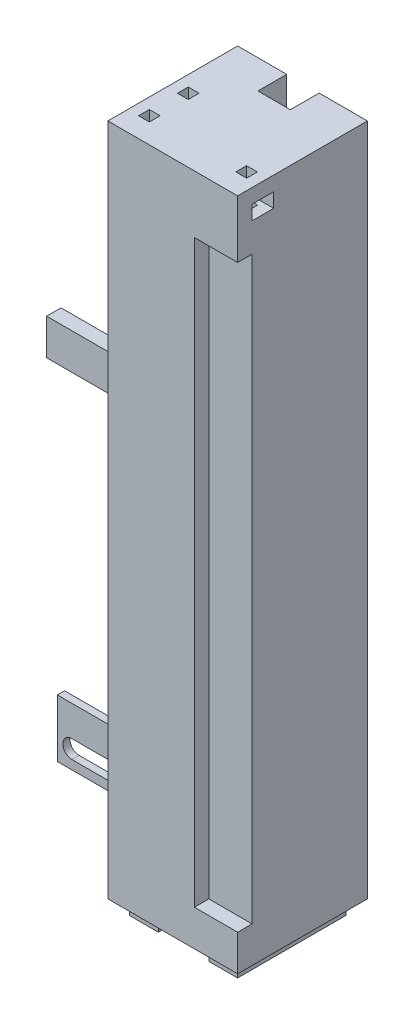
SolidWorks part; units mm, degrees
ref_plane "Front Plane" through (0, 0, 0) normal (0, 0, 1) x (1, 0, 0)
ref_plane "Top Plane" through (0, 0, 0) normal (0, 1, 0) x (1, 0, 0)
ref_plane "Right Plane" through (0, 0, 0) normal (1, 0, 0) x (0, 0, -1)
sketch "Sketch1" plane through (0, 0, 0) normal (0, 1, 0) x (1, 0, 0)
  line L1 (0, 0) -> (36, 0)
  line L2 (0, 0) -> (0, 36)
  line L3 (0, 36) -> (36, 36)
  line L4 (36, 0) -> (36, 36)
  dimension "D1" = 36
  dimension "D2" = 36
extrude "Boss-Extrude1" add sketch "Sketch1" along normal blind 186.9
sketch "Sketch2" plane through (0, 0, 0) normal (0, -1, 0) x (1, 0, 0)
  line L0 (0, 0) -> (36, 0) construction
  line L1 (3, -3) -> (7, -3)
  line L2 (3, -3) -> (3, -33)
  line L3 (3, -33) -> (7, -33)
  line L4 (7, -11) -> (7, -25)
  line L5 (36, -36) -> (0, -36) construction
  line L6 (0, -36) -> (0, 0) construction
  line L20 (36, 0) -> (36, -36) construction
  line L29 (7, -3) -> (11, -3)
  line L31 (7, -11) -> (11, -11)
  line L32 (11, -3) -> (11, -11)
  line L33 (7, -25) -> (11, -25)
  line L35 (7, -33) -> (11, -33)
  line L36 (11, -25) -> (11, -33)
  line L45 (29, -3) -> (33, -3)
  line L46 (29, -11) -> (29, -25)
  line L47 (29, -33) -> (33, -33)
  line L48 (33, -3) -> (33, -33)
  line L50 (29, -3) -> (25, -3)
  line L52 (29, -11) -> (25, -11)
  line L53 (25, -3) -> (25, -11)
  line L54 (29, -33) -> (25, -33)
  line L56 (29, -25) -> (25, -25)
  line L57 (25, -33) -> (25, -25)
  dimension "D1" = 3
  dimension "D2" = 3
  dimension "D3" = 3
  dimension "D4" = 4
  dimension "D5" = 4
  dimension "D6" = 8
  dimension "D7" = 8
  dimension "D8" = 4
  dimension "D9" = 3
  dimension "D10" = 3
  dimension "D11" = 3
  dimension "D12" = 4
  dimension "D13" = 4
  dimension "D14" = 4
extrude "Boss-Extrude2" add sketch "Sketch2" along normal blind 4
sketch "Sketch3" plane through (0, 0, 0) normal (0, -1, 0) x (1, 0, 0)
  line L0 (36, -36) -> (0, -36) construction
  line L2 (0, -36) -> (0, 0) construction
  circle A0 centre (18, -18) radius 2
  dimension "D1" = 4
  dimension "D2" = 18
  dimension "D3" = 18
extrude "Cut-Extrude1" cut sketch "Sketch3" against normal blind 5
sketch "Sketch4" plane through (0, 0, -36) normal (0, 0, 1) x (1, 0, 0)
  line L0 (0, 186.9) -> (36, 186.9) construction
  line L1 (13.62, 186.9) -> (22.62, 186.9)
  line L2 (13.62, 186.9) -> (13.62, 0)
  line L3 (13.62, 0) -> (22.62, 0)
  line L4 (22.62, 186.9) -> (22.62, 0)
  line L5 (0, 0) -> (36, 0) construction
  line L7 (36, 186.9) -> (36, 0) construction
  dimension "D1" = 13.38
  dimension "D2" = 9
extrude "Cut-Extrude2" cut sketch "Sketch4" along normal blind 8
sketch "Sketch5" plane through (36, 0, 0) normal (1, 0, 0) x (0, 0, -1)
  line L0 (0, 186.9) -> (36, 186.9) construction
  line L1 (4, 182.9) -> (10, 182.9)
  line L2 (4, 182.9) -> (4, 178.9)
  line L3 (4, 178.9) -> (10, 178.9)
  line L4 (10, 182.9) -> (10, 178.9)
  line L5 (0, 186.9) -> (0, 0) construction
  dimension "D1" = 6
  dimension "D2" = 4
  dimension "D3" = 4
  dimension "D4" = 4
extrude "Cut-Extrude3" cut sketch "Sketch5" against normal blind 9
sketch "Sketch6" plane through (0, 186.9, 0) normal (0, 1, 0) x (1, 0, 0)
  line L0 (36, 0) -> (36, 36) construction
  line L1 (30, 8.5) -> (33, 8.5)
  line L2 (30, 8.5) -> (30, 5.5)
  line L3 (30, 5.5) -> (33, 5.5)
  line L4 (33, 8.5) -> (33, 5.5)
  line L5 (0, 0) -> (36, 0) construction
  dimension "D1" = 3
  dimension "D2" = 3
  dimension "D3" = 3
  dimension "D4" = 5.5
extrude "Cut-Extrude4" cut sketch "Sketch6" against normal blind 10
sketch "Sketch7" plane through (0, 0, 0) normal (-1, 0, 0) x (0, 0, 1)
  line L0 (-36, 186.9) -> (-36, 0) construction
  line L1 (-28, 0) -> (-26, 0)
  line L2 (-28, 0) -> (-28, 16)
  line L3 (-28, 16) -> (-26, 16)
  line L4 (-26, 0) -> (-26, 16)
  dimension "D1" = 2
  dimension "D2" = 16
  dimension "D3" = 8
extrude "Boss-Extrude3" add sketch "Sketch7" along normal blind 40
sketch "Sketch8" plane through (0, 0, -26) normal (0, 0, 1) x (1, 0, 0)
  line L0 (-40, 0) -> (0, 0) construction
  line L1 (-40, 0) -> (-40, 16) construction
  line L3 (-36, 7.5) -> (-12, 7.5)
  line L5 (-36, 2.5) -> (-12, 2.5)
  arc A0 (-36, 7.5) -> (-36, 2.5) centre (-36, 5) ccw
  arc A1 (-12, 2.5) -> (-12, 7.5) centre (-12, 5) ccw
  dimension "D1" = 5
  dimension "D2" = 5
  dimension "D4" = 5
  dimension "D3" = 4
  dimension "D5" = 5
  dimension "D6" = 24
extrude "Cut-Extrude5" cut sketch "Sketch8" against normal up to next
sketch "Sketch9" plane through (0, 0, 0) normal (-1, 0, 0) x (0, 0, 1)
  line L0 (-26, 0) -> (0, 0) construction
  line L1 (-32, 103.5) -> (-28, 103.5)
  line L2 (-32, 103.5) -> (-32, 93.5)
  line L3 (-32, 93.5) -> (-28, 93.5)
  line L4 (-28, 103.5) -> (-28, 93.5)
  line L5 (-36, 186.9) -> (-36, 0) construction
  dimension "D1" = 103.5
  dimension "D2" = 10
  dimension "D3" = 4
  dimension "D4" = 4
extrude "Boss-Extrude4" add sketch "Sketch9" along normal blind 45
chamfer "Chamfer1" distance 20 angle 45 2 edges at (0, 93.5, -30) (0, 16, -27)
sketch "Sketch10" plane through (0, 0, -26) normal (0, 0, 1) x (1, 0, 0)
  line L0 (-17.1716, 93.5) -> (-2, 78.3284)
  line L1 (-2, 78.3284) -> (-2, 93.5)
  line L2 (-2, 93.5) -> (-17.1716, 93.5)
  line L3 (0, 186.9) -> (0, 0) construction
  line L4 (-20, 93.5) -> (0, 73.5) construction
  line L5 (-45, 93.5) -> (-20, 93.5) construction
  line L6 (-17.1716, 16) -> (-2, 31.1716)
  line L7 (-2, 31.1716) -> (-2, 16)
  line L8 (-2, 16) -> (-17.1716, 16)
  line L9 (0, 36) -> (-20, 16) construction
  line L10 (-40, 16) -> (-20, 16) construction
  dimension "D1" = 2
  dimension "D2" = 2
  dimension "D3" = 0
  dimension "D4" = 2
  dimension "D5" = 2
  dimension "D6" = 0
extrude "Cut-Extrude6" cut sketch "Sketch10" along direction (0, 0, -1) on the side against the normal blind 27
sketch "Sketch11" plane through (0, 0, 0) normal (-1, 0, 0) x (0, 0, 1)
  line L0 (-36, 186.9) -> (0, 186.9) construction
  line L1 (-4, 182.9) -> (-10, 182.9)
  line L2 (-4, 182.9) -> (-4, 178.9)
  line L3 (-4, 178.9) -> (-10, 178.9)
  line L4 (-10, 182.9) -> (-10, 178.9)
  line L5 (0, 186.9) -> (0, 0) construction
  line L7 (-14.8, 182.9) -> (-20.8, 182.9)
  line L8 (-14.8, 182.9) -> (-14.8, 178.9)
  line L9 (-14.8, 178.9) -> (-20.8, 178.9)
  line L10 (-20.8, 182.9) -> (-20.8, 178.9)
  line L11 (-16, 172.9) -> (-10, 172.9)
  line L12 (-16, 172.9) -> (-16, 166.9)
  line L13 (-16, 166.9) -> (-10, 166.9)
  line L14 (-10, 172.9) -> (-10, 166.9)
  dimension "D1" = 6
  dimension "D2" = 4
  dimension "D3" = 4
  dimension "D4" = 4
  dimension "D5" = 6
  dimension "D6" = 4.8
  dimension "D7" = 6
  dimension "D8" = 6
  dimension "D9" = 6
  dimension "D10" = 6
  dimension "D11" = 4
extrude "Cut-Extrude7" cut sketch "Sketch11" against normal blind 9
sketch "Sketch12" plane through (0, 186.9, 0) normal (0, 1, 0) x (1, 0, 0)
  line L0 (0, 0) -> (36, 0) construction
  line L1 (3, 8.5) -> (6, 8.5)
  line L2 (3, 8.5) -> (3, 5.5)
  line L3 (3, 5.5) -> (6, 5.5)
  line L4 (6, 8.5) -> (6, 5.5)
  line L5 (0, 36) -> (0, 0) construction
  line L7 (6, 16.3) -> (3, 16.3)
  line L8 (6, 16.3) -> (6, 19.3)
  line L9 (6, 19.3) -> (3, 19.3)
  line L10 (3, 16.3) -> (3, 19.3)
  dimension "D1" = 3
  dimension "D2" = 3
  dimension "D3" = 5.5
  dimension "D4" = 3
  dimension "D5" = 3
  dimension "D6" = 3
  dimension "D7" = 7.8
extrude "Cut-Extrude8" cut sketch "Sketch12" against normal blind 10
sketch "Sketch13" plane through (0, 0, 0) normal (0, 0, 1) x (1, 0, 0)
  line L0 (36, 186.9) -> (36, 0) construction
  line L1 (24, 170.9) -> (36, 170.9)
  line L2 (24, 170.9) -> (24, 10)
  line L3 (24, 10) -> (36, 10)
  line L4 (36, 170.9) -> (36, 10)
  line L5 (0, 186.9) -> (36, 186.9) construction
  line L6 (0, 0) -> (36, 0) construction
  dimension "D1" = 12
  dimension "D2" = 16
  dimension "D3" = 10
extrude "Cut-Extrude9" cut sketch "Sketch13" against normal blind 4
